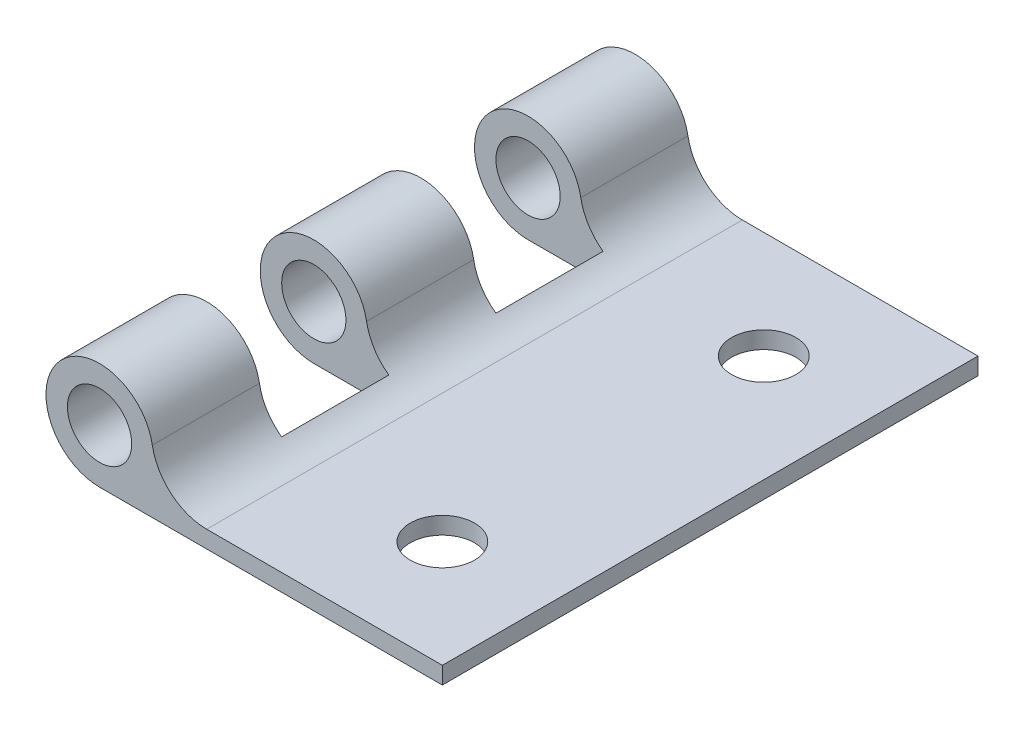
SolidWorks part; units mm, degrees
material "Aço cromo inoxidável"
ref_plane "Plano frontal" through (0, 0, 0) normal (0, 0, 1) x (1, 0, 0)
ref_plane "Plano superior" through (0, 0, 0) normal (0, 1, 0) x (1, 0, 0)
ref_plane "Plano direito" through (0, 0, 0) normal (1, 0, 0) x (0, 0, -1)
sketch "Esboço1" plane through (0, 0, 0) normal (0, 0, 1) x (1, 0, 0)
  line L0 (0, 0) -> (-16, 0)
  line L2 (-11, 0.8) -> (0, 0.8)
  line L3 (0, 0.8) -> (0, 0)
  arc A0 (-16, 0) -> (-15.9579, 4.9996) centre (-16, 2.5) cw
  arc A1 (-15.9579, 4.9996) -> (-13.5375, 2.9315) centre (-16, 2.5) cw
  arc A2 (-13.5375, 2.9315) -> (-11, 0.8) centre (-11, 3.3762) ccw
  circle A3 centre (-16, 2.5) radius 1.5
  circle A4 centre (-16, 2.5) radius 1.5 construction
  dimension "D4" = 16
  dimension "D5" = 1
  dimension "D1" = 0.8
  dimension "D3" = 5
extrude "Ressalto-extrusão1" add sketch "Esboço1" along normal blind 25
sketch "Esboço2" plane through (0, 0, 0) normal (0, -1, 0) x (1, 0, 0)
  line L0 (-18.5, 25) -> (-18.5, 0) construction
  line L1 (-18.5, 5) -> (-12.5, 5)
  line L2 (-18.5, 5) -> (-18.5, 10)
  line L3 (-18.5, 10) -> (-12.5, 10)
  line L4 (-12.5, 5) -> (-12.5, 10)
  line L5 (0, 25) -> (0, 0) construction
  line L6 (0, 25) -> (-11, 25) construction
  line L7 (-18.5, 15) -> (-18.5, 20)
  line L8 (-18.5, 15) -> (-12.5, 15)
  line L9 (-12.5, 15) -> (-12.5, 20)
  line L10 (-18.5, 20) -> (-12.5, 20)
  line L11 (-18.5, 25) -> (-18.5, 30)
  line L12 (-18.5, 25) -> (-12.5, 25)
  line L13 (-12.5, 25) -> (-12.5, 30)
  line L14 (-18.5, 30) -> (-12.5, 30)
  line L15 (-18.5, 0) -> (-13.5375, 0) construction
  line L16 (0, 12.5) -> (-6.2647, 12.5) construction
  line L17 (0, 25) -> (0, 0) construction
  circle A0 centre (-5, 20) radius 1.5
  circle A1 centre (-5, 5) radius 1.5
  dimension "D8" = 3
  dimension "D1" = 5
  dimension "D2" = 3
  dimension "D3" = 5
  dimension "D4" = 5
  dimension "D5" = 6
  dimension "D6" = 5
  dimension "D7" = 5
extrude "Corte-extrusão1" cut sketch "Esboço2" against normal through all
